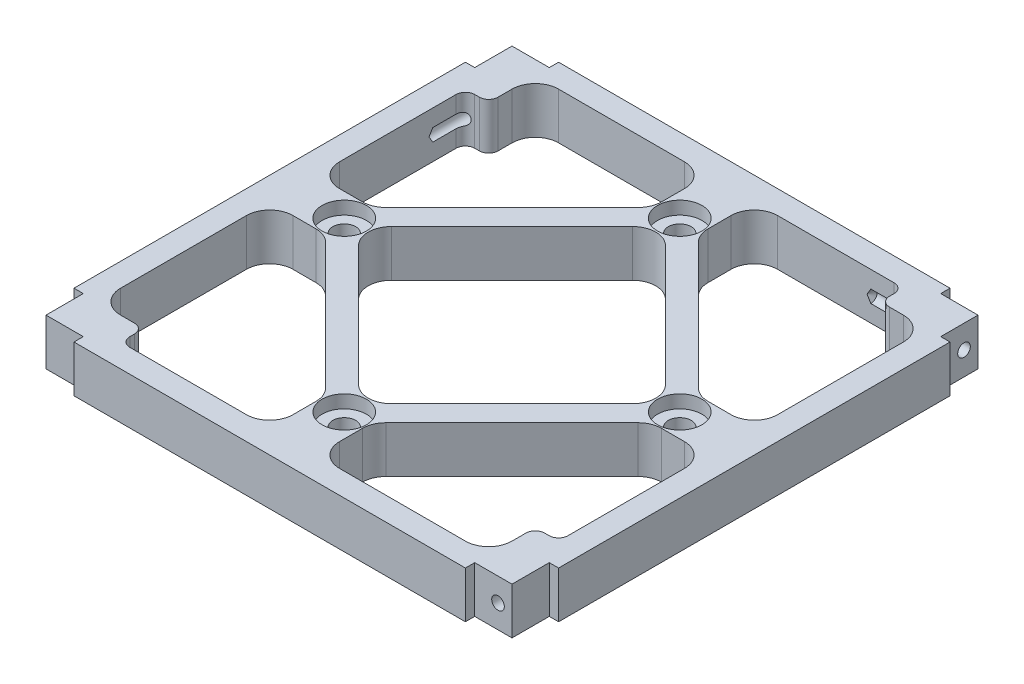
SolidWorks part; units mm, degrees
material "6061-T6 (SS)"
ref_plane "Front Plane" through (0, 0, 0) normal (0, 0, 1) x (1, 0, 0)
ref_plane "Top Plane" through (0, 0, 0) normal (0, 1, 0) x (1, 0, 0)
ref_plane "Right Plane" through (0, 0, 0) normal (1, 0, 0) x (0, 0, -1)
sketch "Sketch1" plane through (0, 0, 0) normal (0, 1, 0) x (1, 0, 0)
  line L0 (-42, 47) -> (-42, 37)
  line L1 (-52, 52) -> (52, 52)
  line L2 (-52, 52) -> (-52, -52)
  line L3 (-52, -52) -> (52, -52)
  line L4 (52, 52) -> (52, -52)
  line L5 (-47, 5) -> (-35, 5)
  line L6 (-35, 5) -> (-5, 35)
  line L7 (-5, 35) -> (-5, 47)
  line L8 (-5, 47) -> (-42, 47)
  line L9 (0, 0) -> (0, 76.3292) construction
  line L10 (0, 0) -> (-78.8537, 0) construction
  line L11 (0, 0) -> (-66.7994, 66.7994) construction
  line L12 (-32.9289, 0) -> (0, 32.9289)
  line L13 (0, 32.9289) -> (32.9289, 0)
  line L14 (32.9289, 0) -> (0, -32.9289)
  line L15 (0, -32.9289) -> (-32.9289, 0)
  line L16 (5, 47) -> (5, 35)
  line L17 (37, 47) -> (5, 47)
  line L18 (37, 42) -> (37, 47)
  line L19 (47, 42) -> (37, 42)
  line L20 (47, 5) -> (47, 42)
  line L21 (35, 5) -> (47, 5)
  line L22 (5, 35) -> (35, 5)
  line L23 (47, -5) -> (35, -5)
  line L24 (47, -37) -> (47, -5)
  line L25 (42, -37) -> (47, -37)
  line L26 (42, -47) -> (42, -37)
  line L27 (5, -47) -> (42, -47)
  line L28 (5, -35) -> (5, -47)
  line L29 (35, -5) -> (5, -35)
  line L30 (-5, -47) -> (-5, -35)
  line L31 (-42, 37) -> (-47, 37)
  line L32 (-47, 37) -> (-47, 5)
  line L33 (-37, -47) -> (-5, -47)
  line L34 (-37, -42) -> (-37, -47)
  line L35 (-47, -42) -> (-37, -42)
  line L36 (-47, -5) -> (-47, -42)
  line L37 (-35, -5) -> (-47, -5)
  line L38 (-5, -35) -> (-35, -5)
  point P36 (0.1996, 0.1996)
  point P45 (0, 0)
  dimension "D1" = 104
  dimension "D2" = 5
  dimension "D3" = 5
  dimension "D4" = 5
  dimension "D5" = 5
  dimension "D6" = 5
  dimension "D7" = 12
  dimension "D8" = 10
  dimension "D9" = 10
  dimension "D10" = 4
extrude "Boss-Extrude1" add sketch "Sketch1" along normal blind 10
fillet "Fillet1" radius 5 24 edges at (32.9289, 5, 0) (0, 5, 32.9289) (-32.9289, 5, 0) (0, 5, -32.9289) (-5, 5, -47) (-5, 5, -35) (-35, 5, -5) (-47, 5, 42) (-47, 5, 5) (-35, 5, 5) (-5, 5, 35) (-5, 5, 47) (42, 5, 47) (47, 5, 5) (35, 5, 5) (5, 5, 35) (5, 5, 47) (47, 5, -42) (47, 5, -5) (35, 5, -5) (5, 5, -35) (5, 5, -47) (-42, 5, -47) (-47, 5, -5)
sketch "Sketch2" plane through (0, 10, 0) normal (0, 1, 0) x (1, 0, 0)
  line L0 (-52, 52) -> (-42, 52)
  line L1 (52, 52) -> (-52, 52) construction
  line L2 (-42, 52) -> (-42, 50)
  line L3 (-42, 50) -> (-50, 50)
  line L4 (-50, 50) -> (-50, 42)
  line L5 (-50, 42) -> (-52, 42)
  line L6 (-52, 52) -> (-52, -52) construction
  line L7 (-52, 42) -> (-52, 52)
  dimension "D1" = 2
  dimension "D2" = 10
extrude "Cut-Extrude1" cut sketch "Sketch2" against normal through all
ref_axis "Axis1" through (0, 10.5, 0) along (0, -1, 0)
pattern_circular "CirPattern1" count 4 over 360 about axis through (0, 10.5, 0) along (0, -1, 0) of "Cut-Extrude1"
hole_wizard "CBORE for #6 Binding Head Machine Screw1" positions "Sketch3" profile "Sketch5" counterbore size "#6" standard "ANSI Inch" end condition through all
sketch "Sketch3" plane through (0, 10, 0) normal (0, 1, 0) x (1, 0, 0)
  line L2 (0, 36) -> (36, 0)
  line L3 (-36, 0) -> (0, -36)
  line L4 (36, 0) -> (0, -36)
  line L6 (0, 0) -> (0, 48.9753) construction
  line L7 (0, 0) -> (-18.2924, 0) construction
  line L9 (-36, 0) -> (0, 36)
  line L11 (-3.5355, 29.3934) -> (-29.3934, 3.5355) construction
  point P0 (0, 36)
  point P199 (-36, 0)
  point P315 (0, -36)
  point P316 (36, 0)
  dimension "D1" = 36
sketch "Sketch5" plane through (0, 10, -36) normal (1, 0, 0) x (0, 0, 1)
  line L0 (0, 0) -> (0, 10)
  line L1 (0, 10) -> (2.4574, 10)
  line L3 (2.4574, 10) -> (2.4575, 2.794)
  line L4 (2.4575, 2.794) -> (4.7625, 2.794)
  line L5 (4.7625, 2.794) -> (4.7625, 0)
  line L7 (4.7625, 0) -> (0, 0)
  line L11 (0, -6.35) -> (0, 107.95) construction
  dimension "Thru Hole Dia." = 4.9149
  dimension "Thru Hole Depth" = 10
  dimension "C'Bore Dia." = 9.525
  dimension "C'Bore Depth" = 2.794
fillet "Fillet3" radius 2 8 edges at (-37, 5, 42) (-37, 5, 47) (42, 5, 37) (47, 5, 37) (37, 5, -42) (37, 5, -47) (-47, 5, -37) (-42, 5, -37)
hole_wizard "#6-32 Tapped Hole1" positions "Sketch6" profile "Sketch9" tap size "#6-32" standard "ANSI Inch"
sketch "Sketch6" plane through (50, 0, 0) normal (1, 0, 0) x (0, 0, -1)
  line L2 (42, 10) -> (52, 0)
  point P0 (47, 5)
  point P13 (47, 5)
sketch "Sketch9" plane through (50, 5, -47) normal (0, 1, 0) x (0, 0, -1)
  line L0 (0, 0) -> (0, 20.8127)
  line L1 (0, 20.8127) -> (1.3525, 20)
  line L2 (1.3525, 20) -> (1.3525, 0)
  line L5 (1.3525, 0) -> (0, 0)
  line L10 (0, 20.8127) -> (-1.3526, 20) construction
  line L11 (0, -6.35) -> (0, 107.95) construction
  dimension "Tap Drill Dia." = 2.7051
  dimension "Tap Drill Depth" = 20
  dimension "Drill Angle" = 118
cosmetic thread "Hole Thread1" parameters "D1"=7.01, "D2"=3.5052
pattern_circular "CirPattern5" count 4 over 360 about axis through (0, 10.5, 0) along (0, -1, 0) of "#6-32 Tapped Hole1"
